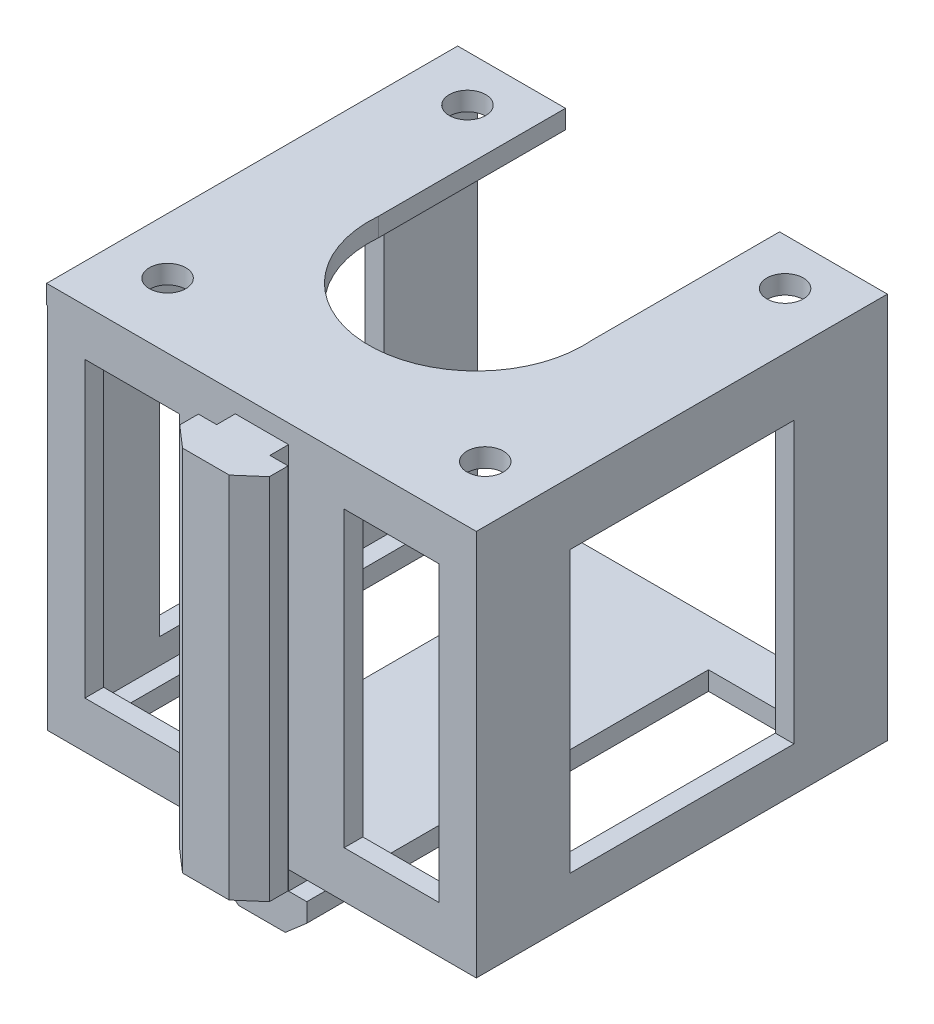
SolidWorks part; units mm, degrees
ref_plane "Front Plane" through (0, 0, 0) normal (0, 0, 1) x (1, 0, 0)
ref_plane "Top Plane" through (0, 0, 0) normal (0, 1, 0) x (1, 0, 0)
ref_plane "Right Plane" through (0, 0, 0) normal (1, 0, 0) x (0, 0, -1)
sketch "Sketch1" plane through (0, 0, 0) normal (0, 0, 1) x (1, 0, 0)
  line L0 (-4.8, -1) -> (-2.85, -1)
  line L2 (-2.85, -1) -> (-2.85, 1)
  line L4 (2.85, -1) -> (2.85, 1)
  line L5 (-2.85, -1) -> (2.85, 1) construction
  line L6 (-2.85, 1) -> (2.85, -1) construction
  line L11 (2.85, -1) -> (4.8, -1)
  line L13 (-2.5, -5) -> (2.5, -5)
  line L15 (-4.8, -3) -> (-2.5, -5)
  line L16 (4.8, -3) -> (2.5, -5)
  line L17 (-4.8, -1) -> (-4.8, -3)
  line L18 (4.8, -1) -> (4.8, -3)
  line L19 (2.85, 1) -> (22.95, 1)
  line L20 (-2.85, 1) -> (-22.95, 1)
  line L21 (-22.95, 1) -> (-22.95, 3)
  line L22 (-22.95, 3) -> (22.95, 3)
  line L23 (22.95, 3) -> (22.95, 1)
  point P0 (0, 0)
  dimension "D1" = 2
  dimension "D2" = 20.1
  dimension "D3" = 20.1
extrude "Boss-Extrude1" add sketch "Sketch1" along normal blind 44
sketch "Sketch3" plane through (0, 0, 44) normal (0, 0, 1) x (1, 0, 0)
  line L0 (-2.85, 1) -> (2.85, 1)
  line L1 (2.85, -1) -> (2.85, 1) construction
  line L2 (-2.85, 1) -> (-4.8, 1)
  line L3 (-22.95, 1) -> (-2.85, 1) construction
  line L4 (2.85, 1) -> (4.8, 1)
  line L5 (2.85, 1) -> (22.95, 1) construction
  line L6 (-4.8, 1) -> (-4.8, 3)
  line L7 (22.95, 3) -> (-22.95, 3) construction
  line L8 (4.8, 1) -> (4.8, 3)
  line L9 (-4.8, 3) -> (4.8, 3)
  dimension "D1" = 1.95
  dimension "D2" = 1.95
extrude "Boss-Extrude3" add sketch "Sketch3" along normal blind 6
sketch "Sketch5" plane through (0, 3, 0) normal (0, 1, 0) x (1, 0, 0)
  line L0 (-4.8, -44) -> (-2.85, -44)
  line L1 (-2.85, -44) -> (-2.85, -46)
  line L2 (-2.85, -46) -> (-4.8, -46)
  line L3 (-4.8, -50) -> (-4.8, -44) construction
  line L4 (-4.8, -46) -> (-4.8, -44)
  dimension "D1" = 1.95
  dimension "D2" = 2
extrude "Cut-Extrude1" cut sketch "Sketch5" against normal blind 6
sketch "Sketch6" plane through (0, 3, 0) normal (0, 1, 0) x (1, 0, 0)
  line L0 (4.8, -44) -> (2.85, -44)
  line L1 (2.85, -44) -> (2.85, -46)
  line L2 (2.85, -46) -> (4.8, -46)
  line L3 (4.8, -50) -> (4.8, -44) construction
  line L4 (4.8, -46) -> (4.8, -44)
  dimension "D1" = 1.95
  dimension "D2" = 2
extrude "Cut-Extrude2" cut sketch "Sketch6" against normal blind 6
sketch "Sketch7" plane through (0, 3, 0) normal (0, 1, 0) x (1, 0, 0)
  line L0 (-4.8, -46) -> (-4.8, -48)
  line L1 (-4.8, -50) -> (-4.8, -46) construction
  line L2 (-4.8, -48) -> (-4.8, -50)
  line L3 (-4.8, -50) -> (-2.5, -50)
  line L4 (4.8, -50) -> (-4.8, -50) construction
  line L5 (-2.5, -50) -> (2.5, -50)
  line L6 (2.5, -50) -> (4.8, -50)
  line L7 (4.8, -50) -> (4.8, -46) construction
  line L8 (4.8, -50) -> (4.8, -48)
  line L9 (-4.8, -48) -> (-2.5, -50)
  line L10 (2.5, -50) -> (4.8, -48)
  line M4 (4.8, -50) -> (4.8, -46)
  line M15 (-4.8, -50) -> (4.8, -50)
  dimension "D1" = 2
  dimension "D2" = 2.3
  dimension "D3" = 2.3
extrude "Cut-Extrude3" cut sketch "Sketch7" against normal blind 6 contours L10 M15 M4 region at (4.0333, 3, 49.3333)
sketch "Sketch8" plane through (0, 3, 0) normal (0, 1, 0) x (1, 0, 0)
  line L0 (-4.8, -46) -> (-4.8, -48)
  line L1 (-4.8, -50) -> (-4.8, -46) construction
  line L2 (-4.8, -48) -> (-4.8, -50)
  line L3 (-4.8, -50) -> (-2.5, -50)
  line L4 (2.5, -50) -> (-4.8, -50) construction
  line L5 (-2.5, -50) -> (-4.8, -48)
  line M13 (-4.8, -46) -> (-4.8, -50)
  line M14 (-4.8, -50) -> (2.5, -50)
  dimension "D1" = 2.3
extrude "Cut-Extrude4" cut sketch "Sketch8" against normal blind 6 contours L5 M14 M13 region at (-4.0333, 3, 49.3333)
sketch "Sketch9" plane through (0, 3, 0) normal (0, 1, 0) x (1, 0, 0)
  line L0 (-22.95, 0) -> (-20.95, 0)
  line L1 (22.95, 0) -> (-22.95, 0) construction
  line L2 (-20.95, 0) -> (-20.95, -42)
  line L3 (-20.95, -42) -> (20.95, -42)
  line L4 (20.95, -42) -> (20.95, 0)
  line L5 (20.95, 0) -> (22.95, 0)
  line L6 (22.95, 0) -> (22.95, -44)
  line L7 (22.95, -44) -> (2.85, -44)
  line L9 (-2.85, -44) -> (-22.95, -44)
  line L10 (-22.95, -44) -> (-22.95, 0)
  line L11 (2.85, -44) -> (2.85, -46)
  line L12 (2.85, -46) -> (4.8, -46)
  line L13 (4.8, -46) -> (4.8, -48)
  line L14 (4.8, -48) -> (2.5, -50)
  line L15 (2.5, -50) -> (-2.5, -50)
  line L16 (-2.5, -50) -> (-4.8, -48)
  line L17 (-4.8, -48) -> (-4.8, -46)
  line L18 (-4.8, -46) -> (-2.85, -46)
  line L19 (-2.85, -46) -> (-2.85, -44)
  dimension "D1" = 2
  dimension "D2" = 2
  dimension "D3" = 2
extrude "Boss-Extrude4" add sketch "Sketch9" along normal blind 37.4
sketch "Sketch11" plane through (0, 0, 0) normal (0, 0, -1) x (-1, 0, 0)
  line L1 (-22.95, 40.4) -> (-20.95, 40.4)
  line L2 (-22.95, 40.4) -> (-22.95, 42.4)
  line L3 (-22.95, 42.4) -> (-20.95, 42.4)
  line L4 (-20.95, 40.4) -> (-20.95, 42.4)
  dimension "D1" = 2
  dimension "D2" = 2
extrude "Boss-Extrude5" add sketch "Sketch11" against normal blind 44
sketch "Sketch12" plane through (20.95, 0, 0) normal (-1, 0, 0) x (0, 0, 1)
  line L0 (42, 40.4) -> (42, 42.4)
  line L1 (44, 42.4) -> (0, 42.4) construction
  line L2 (42, 42.4) -> (44, 42.4)
  line L3 (44, 42.4) -> (44, 40.4)
  line L4 (44, 40.4) -> (42, 40.4)
extrude "Boss-Extrude6" add sketch "Sketch12" along normal blind 44
sketch "Sketch13" plane through (20.95, 0, 0) normal (-1, 0, 0) x (0, 0, 1)
  line L0 (42, 42.4) -> (42, 40.4)
  line L1 (42, 42.4) -> (42, 3) construction
  line L2 (42, 40.4) -> (0, 40.4)
  line L3 (0, 42.4) -> (0, 3) construction
  line L4 (0, 40.4) -> (0, 42.4)
  line L5 (0, 42.4) -> (42, 42.4)
  dimension "D1" = 2
extrude "Boss-Extrude7" add sketch "Sketch13" along normal blind 44
sketch "Sketch14" plane through (0, 40.4, 0) normal (0, -1, 0) x (1, 0, 0)
  line L0 (-23.05, 44) -> (-23.05, 0) construction
  line L2 (-23.05, 0) -> (22.95, 0) construction
  circle A0 centre (-0.05, 21) radius 11.5
  dimension "D1" = 23
  dimension "D2" = 23
  dimension "D3" = 21
extrude "Cut-Extrude5" cut sketch "Sketch14" against normal blind 2
sketch "Sketch15" plane through (0, 42.4, 0) normal (0, 1, 0) x (1, 0, 0)
  line L0 (-23.05, -22) -> (-11.5064, -22)
  line L1 (-23.05, -44) -> (-23.05, 0) construction
  line L2 (-11.5064, -22) -> (-11.5064, 0)
  line L3 (-23.05, 0) -> (22.95, 0) construction
  line L4 (22.95, -22) -> (11.4064, -22)
  line L5 (22.95, -44) -> (22.95, 0) construction
  line L6 (11.4064, -22) -> (11.4064, 0)
  line L7 (11.4064, 0) -> (-11.5064, 0)
  line L8 (-11.5064, -22) -> (11.4064, -22)
  circle A0 centre (-0.05, -21) radius 11.5 construction
extrude "Cut-Extrude7" cut sketch "Sketch15" against normal blind 2 contours L4 L6 L5 L2 region at (-0.05, 42.4, 11)
sketch "Sketch16" plane through (0, 42.4, 0) normal (0, 1, 0) x (1, 0, 0)
  line L0 (-23.05, 0) -> (-11.5064, 0) construction
  line L1 (-23.05, -44) -> (-23.05, 0) construction
  line L2 (11.4064, 0) -> (22.95, 0) construction
  line L3 (22.95, -44) -> (22.95, 0) construction
  line L4 (-23.05, -44) -> (22.95, -44) construction
  circle A0 centre (-17.05, -4.95) radius 1.95
  circle A1 centre (16.95, -4.95) radius 1.95
  circle A2 centre (-17.05, -37.05) radius 1.95
  circle A3 centre (16.95, -37.05) radius 1.95
  dimension "D1" = 4.95
  dimension "D2" = 6
  dimension "D3" = 3.9
  dimension "D4" = 3.9
  dimension "D5" = 4.95
  dimension "D6" = 6
  dimension "D7" = 3.9
  dimension "D8" = 3.9
  dimension "D9" = 6.95
  dimension "D10" = 6.95
  dimension "D11" = 6
extrude "Cut-Extrude9" cut sketch "Sketch16" against normal blind 2
sketch "Sketch18" plane through (-22.95, 0, 0) normal (-1, 0, 0) x (0, 0, 1)
  line L0 (22, 1) -> (22, 44.3731) construction
  line L1 (44, 1) -> (0, 1) construction
  line L2 (44, 20.7) -> (0, 20.7) construction
  line L3 (44, 1) -> (44, 40.4) construction
  line L4 (0, 1) -> (0, 42.4) construction
  line L5 (0, 40.4) -> (0, 1) construction
  line L6 (34, 5.7) -> (10, 5.7)
  line L7 (34, 5.7) -> (34, 35.7)
  line L8 (34, 35.7) -> (10, 35.7)
  line L9 (10, 5.7) -> (10, 35.7)
  line L10 (34, 5.7) -> (10, 35.7) construction
  line L11 (34, 35.7) -> (10, 5.7) construction
  line L12 (44, 40.4) -> (44, 1) construction
  point P10 (22, 20.7)
  dimension "D1" = 30
  dimension "D2" = 10
  dimension "D3" = 10
extrude "Cut-Extrude11" cut sketch "Sketch18" against normal through all
sketch "Sketch19" plane through (0, 1, 0) normal (0, -1, 0) x (1, 0, 0)
  line L0 (-22.95, 44) -> (-2.85, 44) construction
  line L1 (-19.05, 5) -> (-8.8, 5)
  line L2 (-19.05, 5) -> (-19.05, 39)
  line L3 (-19.05, 39) -> (-8.8, 39)
  line L4 (-8.8, 5) -> (-8.8, 39)
  line L5 (-19.05, 5) -> (-8.8, 39) construction
  line L6 (-19.05, 39) -> (-8.8, 5) construction
  line L7 (8.8, 39) -> (18.95, 39)
  line L8 (8.8, 39) -> (8.8, 5)
  line L9 (8.8, 5) -> (18.95, 5)
  line L10 (18.95, 39) -> (18.95, 5)
  line L11 (-22.95, 0) -> (-2.85, 0) construction
  line L12 (-23.05, 0) -> (-23.05, 44) construction
  line L13 (-4.8, 44) -> (-4.8, 0) construction
  line L14 (2.85, 44) -> (22.95, 44) construction
  line L15 (2.85, 0) -> (22.95, 0) construction
  line L16 (22.95, 44) -> (22.95, 0) construction
  line L17 (4.8, 44) -> (4.8, 0) construction
  point P0 (-13.925, 22)
  dimension "D1" = 5
  dimension "D2" = 5
  dimension "D3" = 4
  dimension "D4" = 4
  dimension "D5" = 5
  dimension "D6" = 5
  dimension "D7" = 4
  dimension "D8" = 4
extrude "Cut-Extrude13" cut sketch "Sketch19" against normal blind 2
sketch "Sketch20" plane through (0, 0, 44) normal (0, 0, 1) x (1, 0, 0)
  line L0 (-23.05, 42.4) -> (22.95, 42.4) construction
  line L1 (-18.95, 37.4) -> (-8.8, 37.4)
  line L2 (-18.95, 37.4) -> (-18.95, 6)
  line L3 (-18.95, 6) -> (-8.8, 6)
  line L4 (-8.8, 37.4) -> (-8.8, 6)
  line L5 (8.8, 37.4) -> (18.95, 37.4)
  line L6 (8.8, 37.4) -> (8.8, 6)
  line L7 (8.8, 6) -> (18.95, 6)
  line L8 (18.95, 37.4) -> (18.95, 6)
  line L9 (-22.95, 1) -> (-2.85, 1) construction
  line L10 (-22.95, 40.4) -> (-22.95, 1) construction
  line L11 (-4.8, 1) -> (-4.8, 40.4) construction
  line L12 (2.85, 1) -> (22.95, 1) construction
  line L13 (22.95, 1) -> (22.95, 42.4) construction
  line L14 (4.8, 1) -> (4.8, 40.4) construction
  dimension "D1" = 5
  dimension "D2" = 5
  dimension "D3" = 4
  dimension "D4" = 4
  dimension "D5" = 5
  dimension "D6" = 5
  dimension "D7" = 4
  dimension "D8" = 4
extrude "Cut-Extrude14" cut sketch "Sketch20" against normal blind 2
